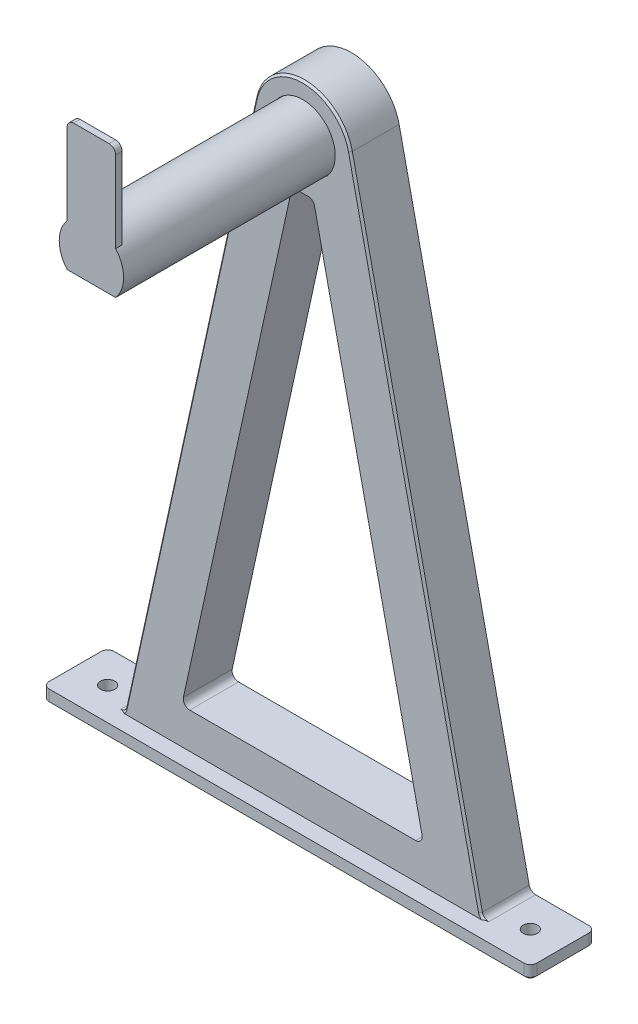
SolidWorks part; units mm, degrees
ref_plane "Front Plane" through (0, 0, 0) normal (0, 0, 1) x (1, 0, 0)
ref_plane "Top Plane" through (0, 0, 0) normal (0, 1, 0) x (1, 0, 0)
ref_plane "Right Plane" through (0, 0, 0) normal (1, 0, 0) x (0, 0, -1)
sketch "Sketch1" plane through (0, 0, 0) normal (0, 0, 1) x (1, 0, 0)
  line L1 (0, 0) -> (0, 4)
  line L2 (0, 4) -> (-20, 4)
  line L5 (-130, 4) -> (-150, 4)
  line L6 (-150, 4) -> (-150, 0)
  line L8 (-150, 0) -> (0, 0)
  line L9 (-75, 200) -> (-75, 0) construction
  line L10 (-130, 4) -> (-89.6526, 188.2094)
  line L11 (-60.3474, 188.2094) -> (-20, 4)
  line L12 (-112.2351, 15) -> (-78.2094, 170.3474)
  line L13 (-71.7906, 170.3474) -> (-37.7649, 15)
  line L14 (-37.7649, 15) -> (-112.2351, 15)
  line L15 (-99.8856, 141.4901) -> (-85.2329, 138.2808) construction
  line L16 (-75, 0) -> (-75, 15) construction
  line L17 (-40.1737, 96.1047) -> (-54.8263, 92.8953) construction
  line L18 (-82.5, 178.3856) -> (-67.5, 178.3856)
  line L19 (-82.4547, 178.4856) -> (-67.5453, 178.4856)
  arc A0 (-78.2094, 170.3474) -> (-71.7906, 170.3474) centre (-75, 185) ccw
  arc A1 (-67.5, 178.3856) -> (-82.5, 178.3856) centre (-75, 185) ccw
  arc A2 (-60.3474, 188.2094) -> (-89.6526, 188.2094) centre (-75, 185) ccw
  arc A3 (-67.5453, 178.4856) -> (-82.4547, 178.4856) centre (-75, 185) ccw
  dimension "D5" = 30
  dimension "D8" = 20
  dimension "D10" = 0.1
  dimension "D1" = 20
  dimension "D2" = 200
  dimension "D3" = 150
  dimension "D4" = 4
  dimension "D6" = 15
  dimension "D7" = 15
  dimension "D9" = 15
  dimension "D11" = 0.1
extrude "Boss-Extrude1" add sketch "Sketch1" along normal blind 20 contours L11 A2 L10 L5 L6 L8 L1 L2 L12 A0 L13 L14 A1 L18 region at (-75, 2.5, 0)
sketch "Sketch2" plane through (0, 0, 20) normal (0, 0, 1) x (1, 0, 0)
  line L0 (-60.3474, 188.2094) -> (-20, 4) construction
  line L1 (-130, 4) -> (-20, 4)
  line L2 (-130, 4) -> (-130, 236.9351)
  line L3 (-130, 236.9351) -> (-20, 236.9351)
  line L4 (-20, 4) -> (-20, 236.9351)
  line L5 (-130, 4) -> (-150, 4) construction
  line L6 (-130, 4) -> (-89.6526, 188.2094) construction
  point P5 (0, 0)
  point P6 (-20, 5)
  point P10 (-85, 5)
  point P15 (-130, 236.9351)
extrude "Cut-Extrude1" cut sketch "Sketch2" against normal blind 5
extrude "Boss-Extrude2" add sketch "Sketch1<3>" along normal blind 80 separate body contours L19 A3 region at (-75, 186.012, 0)
sketch "Sketch1<3>" plane through (0, 0, 0) normal (0, 0, 1) x (1, 0, 0) same geometry as "Sketch1"
sketch "Sketch3" plane through (0, 0, 80) normal (0, 0, 1) x (1, 0, 0)
  line L1 (-82.4547, 218.4856) -> (-67.5453, 218.4856)
  line L2 (-82.4547, 218.4856) -> (-82.4547, 178.4856)
  line L3 (-82.4547, 178.4856) -> (-67.5453, 178.4856)
  line L4 (-67.5453, 218.4856) -> (-67.5453, 178.4856)
  arc A1 (-67.5453, 178.4856) -> (-82.4547, 178.4856) centre (-75, 185) ccw construction
  point P4 (-45.0453, 83.4856)
  point P5 (-59.991, 83.5274)
  point P6 (-45.0453, 83.4856)
  point P7 (-45.9973, 83.3856)
  point P10 (-59.9547, 83.4856)
  point P11 (-45.1339, 83.3856)
  dimension "D1" = 40
extrude "Boss-Extrude3" add sketch "Sketch3" against normal blind 2
sketch "Sketch4" plane through (0, 4, 0) normal (0, 1, 0) x (1, 0, 0)
  line L0 (-130, 0) -> (-150, -20) construction
  line L1 (-20, 0) -> (0, -20) construction
  circle A0 centre (-140, -10) radius 2.2
  circle A1 centre (-10, -10) radius 2.2
  dimension "D1" = 4.4
  dimension "D2" = 4.4
extrude "Cut-Extrude2" cut sketch "Sketch4" against normal up to surface (4 mm away) up to face at (-75, 0, 10)
fillet "Fillet1" radius 2 10 edges at (-20, 4, 7.5) (-130, 4, 7.5) (-37.7649, 15, 7.5) (-112.2351, 15, 7.5) (-71.7906, 170.3474, 7.5) (-78.2094, 170.3474, 7.5) (0, 2, 0) (0, 2, 20) (-150, 2, 20) (-150, 2, 0)
chamfer "Chamfer1" distance 0.6 angle 45 10 edges at (-75, 0, 20) (-149.4142, 0, 19.4142) (-0.5858, 0, 19.4142) (-150, 0, 10) (0, 0, 10) (-149.4142, 0, 0.5858) (-0.5858, 0, 0.5858) (-75, 0, 0) (-12.2, 0, 10) (-142.2, 0, 10)
chamfer "Chamfer2" distance 1 angle 45 2 edges at (-75, 194.9, 0) (-75, 178.4856, 0)
fillet "Fillet2" radius 2 2 edges at (-67.5453, 218.4856, 79) (-82.4547, 218.4856, 79)
chamfer "Chamfer3" distance 0.6 angle 45 5 edges at (-19.6445, 4.4418, 15) (-40.3458, 96.8907, 15) (-75, 200, 15) (-130.3555, 4.4418, 15) (-109.6542, 96.8907, 15)
